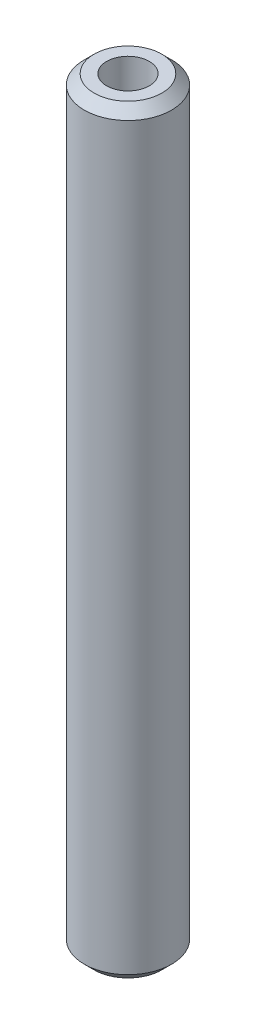
SolidWorks part; units mm, degrees
ref_plane "Front Plane" through (0, 0, 0) normal (0, 0, 1) x (1, 0, 0)
ref_plane "Top Plane" through (0, 0, 0) normal (0, 1, 0) x (1, 0, 0)
ref_plane "Right Plane" through (0, 0, 0) normal (1, 0, 0) x (0, 0, -1)
sketch "Sketch1" plane through (0, 0, 0) normal (0, 1, 0) x (1, 0, 0)
  circle A0 centre (0, 0) radius 17.5
  dimension "SHAFT_OD" = 35
extrude "Boss-Extrude1" add sketch "Sketch1" along normal blind 304.5294
sketch "Sketch2" plane through (0, 0, 0) normal (0, 1, 0) x (1, 0, 0)
  circle A0 centre (0, 0) radius 8.5363
  dimension "BORE_D" = 17.0727
extrude "Cut-Extrude1" cut sketch "Sketch2" along normal through all
chamfer "Chamfer1" distance 3.9357 angle 45 2 edges at (0, 304.5294, 17.5) (0, 0, 17.5)
